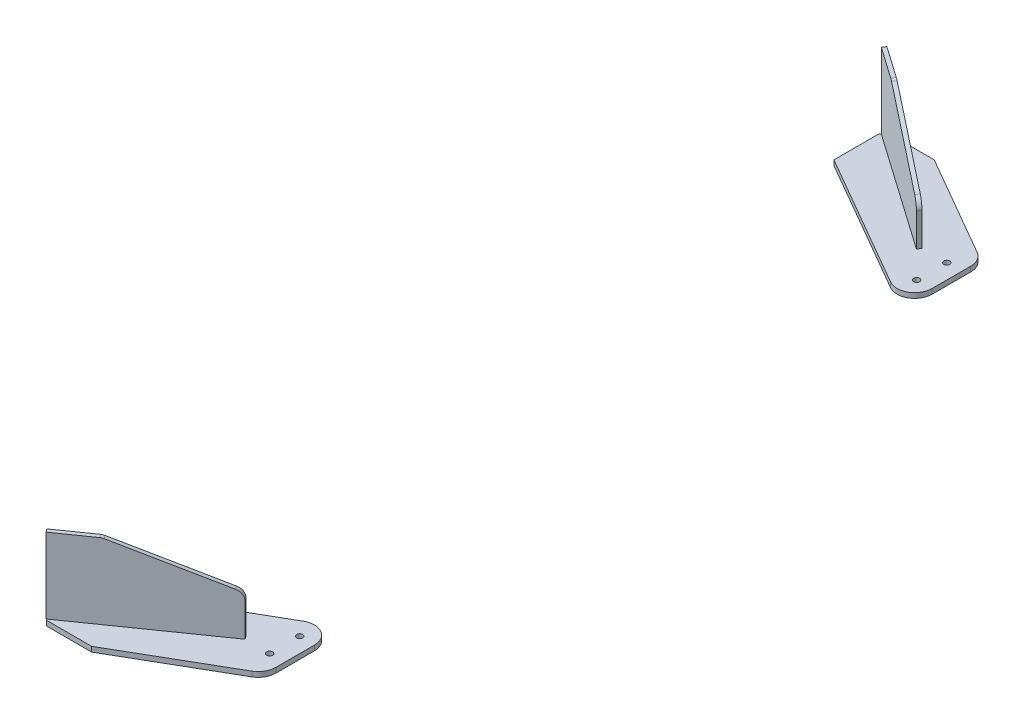
SolidWorks part; units mm, degrees
ref_plane "Front Plane" through (0, 0, 0) normal (0, 0, 1) x (1, 0, 0)
ref_plane "Top Plane" through (0, 0, 0) normal (0, 1, 0) x (1, 0, 0)
ref_plane "Right Plane" through (0, 0, 0) normal (1, 0, 0) x (0, 0, -1)
sketch "Sketch1" plane through (0, 0, 0) normal (0, 1, 0) x (1, 0, 0)
  line L0 (0, 0) -> (0, 163.1526) construction
  line L1 (0, 0) -> (320, 0) construction
  line L2 (0, 0) -> (0, 100) construction
  line L3 (0, 0) -> (100, 0) construction
  line L4 (320, 0) -> (320, 353.7304) construction
  line L5 (0, 100) -> (320, 284.7521) construction
  line L6 (100, 0) -> (320, 127.0171) construction
  line L7 (0, 0) -> (320, 184.7521) construction
  line L8 (290, 0) -> (290, 267.4316) construction
  line L9 (290, 165) -> (320, 165) construction
  line L10 (290, 225) -> (320, 225) construction
  line L11 (100, 0) -> (302.5, 116.9134)
  line L12 (320, 147.2243) -> (320, 224.1303)
  line L13 (267.5, 254.4412) -> (0, 100)
  line L14 (0, 10) -> (10, 0)
  line L15 (0, 100) -> (0, 10)
  line L16 (10, 0) -> (100, 0)
  circle A0 centre (290, 225) radius 6
  circle A1 centre (290, 165) radius 6
  arc A2 (320, 147.2243) -> (302.5, 116.9134) centre (285, 147.2243) cw
  arc A3 (267.5, 254.4412) -> (320, 224.1303) centre (285, 224.1303) cw
  dimension "D7" = 12
  dimension "D10" = 35
  dimension "D1" = 100
  dimension "D2" = 220
  dimension "D3" = 120
  dimension "D4" = 30
  dimension "D5" = 165
  dimension "D6" = 60
  dimension "D8" = 10
  dimension "D9" = 10
extrude "Boss-Extrude1" add sketch "Sketch1" along normal blind 10
sketch "Sketch2" plane through (0, 10, 0) normal (0, 1, 0) x (1, 0, 0)
  line L0 (5, 5) -> (238.4583, 168.4693)
  line L1 (0, 10) -> (10, 0) construction
  line L2 (10, 0) -> (100, 0) construction
  dimension "D1" = 35
  dimension "D2" = 285
extrude "Extrude-Thin1" add sketch "Sketch2" along normal blind 150 separate body thin thin type mid plane wall 8
sketch "Sketch3" plane through (-2.9986, 0, -4.2824) normal (-0.5736, 0, -0.8192) x (-0.8192, 0, 0.5736)
  line L0 (-291.9636, 90) -> (-86.9636, 160) construction
  line L1 (-291.9636, 160) -> (-291.9636, 10) construction
  line L2 (-6.9636, 160) -> (-291.9636, 160) construction
  line L3 (-6.9636, 160) -> (-6.9636, 10) construction
  line L4 (-6.9636, 10) -> (-291.9636, 10) construction
  line L5 (-291.9636, 160) -> (-291.9636, 90)
  line L6 (-291.9636, 90) -> (-86.9636, 160)
  line L7 (-86.9636, 160) -> (-291.9636, 160)
  dimension "D1" = 80
  dimension "D2" = 80
extrude "Cut-Extrude1" cut sketch "Sketch3" against normal up to surface (8 mm away) up to face at (124.0235, 85, -83.458)
fillet "Fillet1" radius 20 2 edges at (70.5322, 160, -50.8861) (238.4583, 90, -168.4693)
sketch "Sketch4" plane through (0, 0, 0) normal (0, -1, 0) x (1, 0, 0)
  line L0 (0, 0) -> (0, -840) construction
  line L1 (16.2116, 0) -> (0, 0) construction
  line L2 (10, 0) -> (100, 0) construction
  line L3 (-351.2039, -840) -> (326.6826, -840) construction
  dimension "D1" = 840
ref_plane "Plane1" through (0, 0, -840) normal (0, 0, 1) x (1, 0, 0)
mirror "Mirror1" about plane through (0, 0, -840) normal (0, 0, 1) of bodies 108 110
